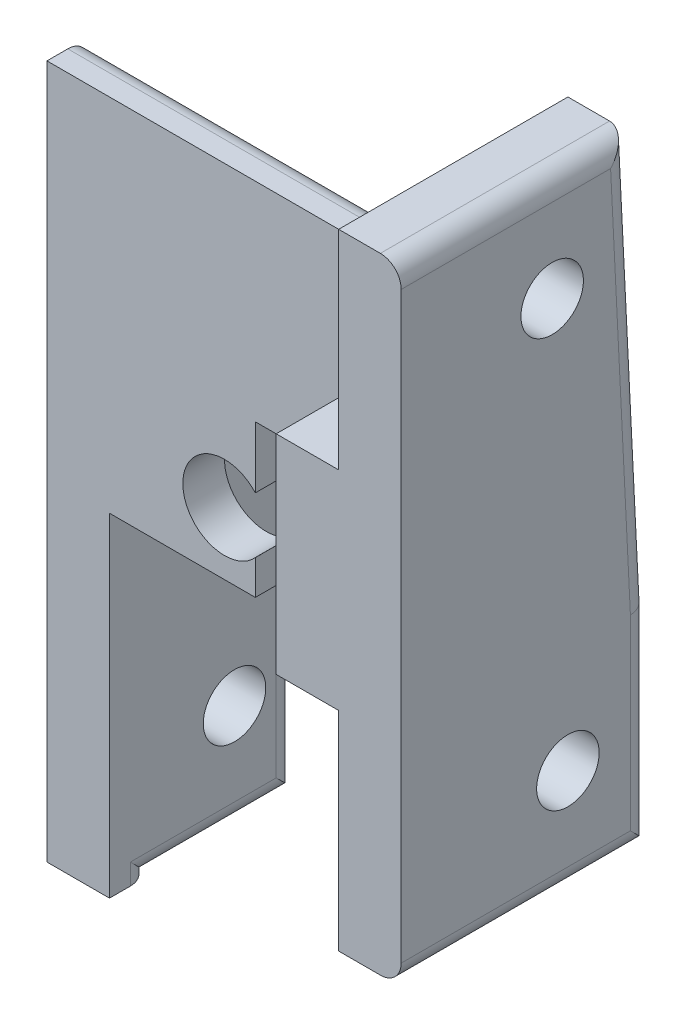
SolidWorks part; units mm, degrees
ref_plane "Alzado" through (0, 0, 0) normal (0, 0, 1) x (1, 0, 0)
ref_plane "Planta" through (0, 0, 0) normal (0, 1, 0) x (1, 0, 0)
ref_plane "Vista lateral" through (0, 0, 0) normal (1, 0, 0) x (0, 0, -1)
sketch "Croquis1" plane through (0, 0, 0) normal (1, 0, 0) x (0, 0, -1)
  line L1 (-24, 0) -> (0, 0)
  line L2 (-24, 0) -> (-24, -33.3)
  line L3 (-24, -33.3) -> (0, -33.3)
  line L4 (0, 0) -> (0, -33.3)
  dimension "D1" = 33.3
  dimension "D2" = 24
extrude "Saliente-Extruir2" add sketch "Croquis1" along normal blind 7
sketch "Croquis3" plane through (0, 0, 0) normal (0, 1, 0) x (1, 0, 0)
  line L0 (7, 0) -> (7, -24) construction
  line L1 (7, -2) -> (3, -2)
  line L2 (7, -2) -> (7, -21)
  line L3 (7, -21) -> (3, -21)
  line L4 (3, -2) -> (3, -21)
  line L5 (7, 0) -> (0, 0) construction
  line L6 (7, -24) -> (0, -24) construction
  line L7 (0, 0) -> (0, -24) construction
  dimension "D1" = 2
  dimension "D2" = 3
  dimension "D3" = 3
extrude "Cortar-Extruir1" cut sketch "Croquis3" against normal through all
sketch "Croquis7" plane through (0, 0, 0) normal (-1, 0, 0) x (0, 0, 1)
  line L0 (24, -33.3) -> (0, -33.3) construction
  line L1 (-7, 15) -> (31, 15)
  line L2 (-7, 15) -> (-7, -44.3)
  line L3 (-7, -44.3) -> (31, -44.3)
  line L4 (31, 15) -> (31, -44.3)
  line L5 (0, 0) -> (24, 0) construction
  line L6 (24, 0) -> (24, -33.3) construction
  line L7 (0, -33.3) -> (0, 0) construction
  line L9 (-7, 15) -> (0, 15)
  line L10 (-7, 15) -> (-7, 0)
  line L11 (-7, 0) -> (0, 0)
  line L12 (0, 15) -> (0, 0)
  line L13 (24, 0) -> (31, 0)
  line L14 (24, 0) -> (24, 15)
  line L15 (24, 15) -> (31, 15)
  line L16 (31, 0) -> (31, 15)
  line L17 (24, -33.3) -> (31, -33.3)
  line L18 (24, -33.3) -> (24, -44.3)
  line L19 (24, -44.3) -> (31, -44.3)
  line L20 (31, -33.3) -> (31, -44.3)
  line L21 (0, -33.3) -> (-7, -33.3)
  line L22 (0, -33.3) -> (0, -44.3)
  line L23 (0, -44.3) -> (-7, -44.3)
  line L24 (-7, -33.3) -> (-7, -44.3)
  circle A0 centre (-4, -15) radius 1.5
  circle A1 centre (-4, -28.3) radius 1.5
  circle A2 centre (28, -28.3) radius 1.5
  circle A3 centre (28, -15) radius 1.5
  circle A4 centre (4, 11) radius 1.5
  circle A5 centre (20, 11) radius 1.5
  circle A6 centre (4, -40.3) radius 1.5
  circle A7 centre (20, -40.3) radius 1.5
  dimension "D6" = 15
  dimension "D7" = 3
  dimension "D9" = 3
  dimension "D10" = 5
  dimension "D12" = 4
  dimension "D13" = 4
  dimension "D14" = 3
  dimension "D15" = 4
  dimension "D16" = 4
  dimension "D17" = 3
  dimension "D18" = 5
  dimension "D19" = 3
  dimension "D20" = 3
  dimension "D21" = 3
  dimension "D22" = 15
  dimension "D23" = 3
  dimension "D24" = 3
  dimension "D25" = 4
  dimension "D26" = 4
  dimension "D27" = 4
  dimension "D28" = 4
  dimension "D5" = 3
  dimension "D8" = 3
  dimension "D11" = 3
  dimension "D1" = 11
  dimension "D2" = 15
  dimension "D3" = 7
  dimension "D4" = 7
extrude "Saliente-Extruir3" add sketch "Croquis7" along normal blind 3 separate body
sketch "Croquis8" plane through (0, 0, 24) normal (0, 0, 1) x (1, 0, 0)
  line L1 (0, 0) -> (18, 0)
  line L2 (0, 0) -> (0, -10)
  line L3 (0, -10) -> (18, -10)
  line L4 (18, 0) -> (18, -10)
  circle A1 centre (15, -5) radius 1.5
  circle A2 centre (3, -5) radius 1.5
  dimension "D3" = 12
  dimension "D2" = 3
  dimension "D5" = 3
  dimension "D6" = 5
  dimension "D4" = 3
  dimension "D7" = 5
  dimension "D1" = 10
  dimension "D8" = 3
extrude "Saliente-Extruir5" add sketch "Croquis8" against normal blind 3
sketch "Croquis9" plane through (0, 0, 0) normal (0, 0, -1) x (-1, 0, 0)
  line L1 (0, 0) -> (-18, 0)
  line L2 (0, 0) -> (0, -10)
  line L3 (0, -10) -> (-18, -10)
  line L4 (-18, 0) -> (-18, -10)
  circle A1 centre (-15, -5) radius 1.5
  dimension "D1" = 3
extrude "Saliente-Extruir6" add sketch "Croquis9" against normal blind 2
sketch "Croquis10" plane through (18, 0, 0) normal (1, 0, 0) x (0, 0, -1)
  line L1 (-24, 0) -> (0, 0)
  line L2 (-24, 0) -> (-24, -10)
  line L3 (-24, -10) -> (0, -10)
  line L4 (0, 0) -> (0, -10)
extrude "Saliente-Extruir7" add sketch "Croquis10" along normal blind 3
sketch "Croquis11" plane through (3, 0, 0) normal (1, 0, 0) x (0, 0, -1)
  line L1 (-21, 0) -> (-2, 0)
  line L2 (-21, 0) -> (-21, -38)
  line L3 (-21, -38) -> (-2, -38)
  line L4 (-2, 0) -> (-2, -38)
  dimension "D1" = 38
  dimension "D2" = 19
extrude "Cortar-Extruir5" cut sketch "Croquis11" against normal through all
sketch "Croquis15" plane through (0, 0, 0) normal (1, 0, 0) x (0, 0, -1)
  line L1 (-31, 0) -> (-24, 0)
  line L2 (-31, 0) -> (-31, -10)
  line L3 (-31, -10) -> (-24, -10)
  line L4 (-24, 0) -> (-24, -10)
  line L5 (0, 0) -> (7, 0)
  line L6 (0, 0) -> (0, -10)
  line L7 (0, -10) -> (7, -10)
  line L8 (7, 0) -> (7, -10)
  line L9 (-31, 0) -> (-31, -33.3) construction
  line L10 (-24, 0) -> (-31, 0) construction
  dimension "D1" = 7
  dimension "D2" = 7
  dimension "D3" = 90
extrude "Cortar-Extruir8" cut sketch "Croquis15" against normal through all
sketch "Croquis16" plane through (0, 0, 0) normal (0, 0, -1) x (-1, 0, 0)
  line L0 (-7, -33.3) -> (-7, -10) construction
  line L1 (-7, -17.3) -> (0, -17.3)
  line L2 (-7, -17.3) -> (-7, -33.3)
  line L3 (-7, -33.3) -> (0, -33.3)
  line L4 (0, -17.3) -> (0, -33.3)
  line L5 (0, -33.3) -> (0, -10) construction
  line L6 (-7, -25.3) -> (0, -25.3) construction
  line L7 (-7, -33.3) -> (0, -33.3) construction
  dimension "D1" = 8
  dimension "D2" = 8
extrude "Cortar-Extruir9" cut sketch "Croquis16" against normal blind 2
sketch "Croquis18" plane through (21, 0, 0) normal (1, 0, 0) x (0, 0, -1)
  line L0 (0, -17.3) -> (0, -10) construction
  line L1 (-24, -10) -> (0, -10)
  line L2 (-24, -10) -> (-24, -20)
  line L3 (-24, -20) -> (0, -20)
  line L4 (0, -10) -> (0, -20)
  line L6 (-24, -10) -> (0, -10)
  line L7 (-24, -10) -> (-24, 10)
  line L8 (-24, 10) -> (-1, 10)
  line L9 (0, -10) -> (-1, 10)
  circle A0 centre (-20, 5) radius 1.5
  circle A1 centre (-4.755, 5) radius 1.5
  circle A2 centre (-20, -15) radius 1.5
  circle A3 centre (-4, -15) radius 1.5
  line M9 (-24, 0) -> (-24, -10)
  line M10 (-24, -10) -> (0, -10)
  line M11 (0, -10) -> (0, 0)
  line M12 (0, 0) -> (-24, 0)
  dimension "D4" = 3
  dimension "D5" = 3
  dimension "D6" = 4
  dimension "D7" = 5
  dimension "D8" = 5
  dimension "D9" = 4
  dimension "D10" = 3
  dimension "D11" = 3
  dimension "D12" = 4
  dimension "D13" = 4
  dimension "D14" = 5
  dimension "D15" = 5
  dimension "D2" = 10
  dimension "D3" = 23
  dimension "D16" = 20
  dimension "D17" = 90
extrude "Saliente-Extruir8" add sketch "Croquis18" along normal blind 3 contours L9 L8 L7 A1 A0 M12 | M12 M9 M10 M11 | L4 L2 L3 A3 A2 M10
fillet "Redondeo1" radius 1 16 edges at (0, -21.65, -7) (0, -10, -3.5) (0, -33.3, -3.5) (0, -44.3, 12) (0, -38.8, 0) (0, -33.3, 27.5) (0, -10, 27.5) (0, -21.65, 31) (24, 10, 12.5) (24, -15, 0) (7, -21.65, 24) (24, -5, 24) (24, -20, 12)
sketch "Croquis19" plane through (0, -44.3, 0) normal (0, -1, 0) x (-1, 0, 0)
  line L0 (3, -12) -> (-26.5, -12) construction
  line L1 (3, 0) -> (3, -24) construction
  line L3 (3, -31) -> (1, -31) construction
  line L4 (3, -12) -> (-24, -12)
  line L5 (3, -12) -> (3, -31)
  line L6 (3, -31) -> (-24, -31)
  line L7 (-24, -12) -> (-24, -31)
  line L8 (-24, -23) -> (-24, -1) construction
  dimension "D1" = 0
  dimension "D2" = 0
extrude "Cortar-Extruir11" cut sketch "Croquis19" against normal through all
sketch "Croquis21" plane through (0, 0, 0) normal (0, 0, -1) x (-1, 0, 0)
  line L0 (0, -17.3) -> (-7, -17.3) construction
  line L1 (-7, -17.3) -> (-7, -10) construction
  circle A0 centre (-5.52, -14.3) radius 2
  dimension "D1" = 4
  dimension "D2" = 3
  dimension "D3" = 1.48
extrude "Cortar-Extruir12" cut sketch "Croquis21" against normal blind 10
sketch "Croquis22" plane through (0, 0, 0) normal (1, 0, 0) x (0, 0, -1)
  line L0 (-12, -38) -> (-12, -43.3) construction
  line L1 (0, -44.3) -> (-12, -44.3)
  line L2 (0, -44.3) -> (0, -33.3)
  line L3 (0, -33.3) -> (-12, -33.3)
  line L4 (-12, -44.3) -> (-12, -33.3)
  dimension "D1" = 0
  dimension "D2" = 11
extrude "Cortar-Extruir13" cut sketch "Croquis22" against normal through all
